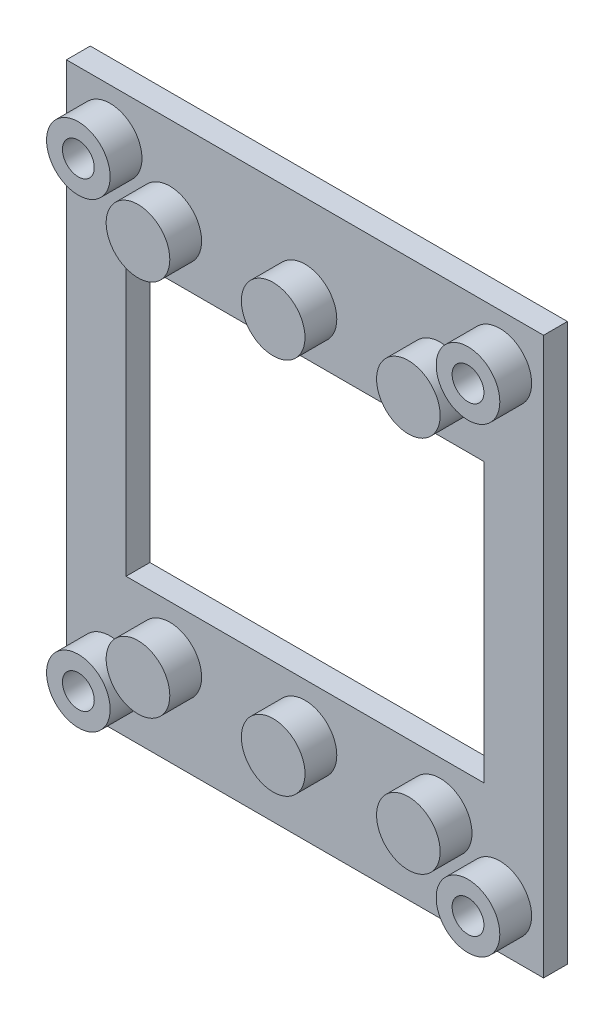
SolidWorks part; units mm, degrees
ref_plane "Plan de face" through (0, 0, 0) normal (0, 0, 1) x (1, 0, 0)
ref_plane "Plan de dessus" through (0, 0, 0) normal (0, 1, 0) x (1, 0, 0)
ref_plane "Plan de droite" through (0, 0, 0) normal (1, 0, 0) x (0, 0, -1)
sketch "Esquisse1" plane through (0, 0, 0) normal (0, 0, 1) x (1, 0, 0)
  line L1 (-30, 35) -> (30, 35)
  line L2 (-30, 35) -> (-30, -35)
  line L3 (-30, -35) -> (30, -35)
  line L4 (30, 35) -> (30, -35)
  line L5 (-30, 35) -> (30, -35) construction
  line L6 (-30, -35) -> (30, 35) construction
  point P0 (0, 0)
  dimension "D1" = 70
  dimension "D2" = 60
base flange "Tôle de base pliée1" sketch "Esquisse1" thickness 3 reverse thickness direction no parameters "D1"=2
sketch "Esquisse6" plane through (0, 0, 0) normal (0, 0, 1) x (1, 0, 0)
  line L1 (-24.5, 29) -> (24.5, 29) construction
  line L2 (-24.5, 29) -> (-24.5, -29) construction
  line L3 (-24.5, -29) -> (24.5, -29) construction
  line L4 (24.5, 29) -> (24.5, -29) construction
  line L5 (-24.5, 29) -> (24.5, -29) construction
  line L6 (-24.5, -29) -> (24.5, 29) construction
  circle A4 centre (-24.5, 29) radius 2
  circle A5 centre (24.5, 29) radius 2
  circle A6 centre (24.5, -29) radius 2
  circle A7 centre (-24.5, -29) radius 2
  point P0 (0, 0)
  dimension "D1" = 4
  dimension "D2" = 49
  dimension "D3" = 58
  dimension "D4" = 2
  dimension "D5" = 2
extrude "Enlèv. mat.-Extru.1" cut sketch "Esquisse6" against normal up to next normal cut yes
sketch "Esquisse7" plane through (0, 0, 0) normal (0, 0, 1) x (1, 0, 0)
  line L0 (0, 23.75) -> (0, -23.75) construction
  circle A0 centre (-17, -23.75) radius 2
  circle A1 centre (0, -23.75) radius 2
  circle A2 centre (17, -23.75) radius 2
  circle A3 centre (0, 23.75) radius 2
  circle A4 centre (17, 23.75) radius 2
  circle A5 centre (-17, 23.75) radius 2
  circle A6 centre (24.5, 29) radius 2 construction
  circle A7 centre (24.5, 29) radius 2 construction
  point P2 (0, 0)
  dimension "D1" = 4
  dimension "D4" = 34
  dimension "D5" = 47.5
  dimension "D2" = 3
  dimension "D3" = 2
extrude "Enlèv. mat.-Extru.2" cut sketch "Esquisse7" against normal up to next normal cut yes
sketch "Esquisse9" plane through (0, 0, 0) normal (0, 0, 1) x (1, 0, 0)
  circle A0 centre (-24.5, 29) radius 4
  circle A1 centre (24.5, 29) radius 4
  circle A2 centre (24.5, -29) radius 4
  circle A3 centre (-24.5, -29) radius 4
  circle A4 centre (-24.5, -29) radius 2 construction
  circle A5 centre (24.5, -29) radius 2 construction
  circle A6 centre (24.5, 29) radius 2 construction
  circle A7 centre (-24.5, 29) radius 2 construction
  circle A8 centre (-24.5, -29) radius 2
  circle A9 centre (24.5, -29) radius 2
  circle A10 centre (24.5, 29) radius 2
  circle A11 centre (-24.5, 29) radius 2
  dimension "D1" = 8
  dimension "D2" = 8
  dimension "D3" = 8
  dimension "D4" = 8
extrude "Boss.-Extru.1" add sketch "Esquisse9" along normal blind 4
sketch "Esquisse10" plane through (0, 0, 0) normal (0, 0, 1) x (1, 0, 0)
  line L1 (-22.5, 17.5) -> (22.5, 17.5)
  line L2 (-22.5, 17.5) -> (-22.5, -17.5)
  line L3 (-22.5, -17.5) -> (22.5, -17.5)
  line L4 (22.5, 17.5) -> (22.5, -17.5)
  line L5 (-22.5, 17.5) -> (22.5, -17.5) construction
  line L6 (-22.5, -17.5) -> (22.5, 17.5) construction
  point P0 (0, 0)
  dimension "D1" = 35
  dimension "D2" = 45
extrude "Enlèv. mat.-Extru.3" cut sketch "Esquisse10" against normal up to next normal cut yes
sketch "Esquisse11" plane through (0, 0, -3) normal (0, 0, -1) x (-1, 0, 0)
  circle A0 centre (-24.5, -29) radius 2 construction
  circle A1 centre (24.5, -29) radius 2 construction
  circle A2 centre (24.5, 29) radius 2 construction
  circle A3 centre (-24.5, 29) radius 2 construction
  circle A4 centre (-24.5, -29) radius 2
  circle A5 centre (24.5, -29) radius 2
  circle A6 centre (24.5, 29) radius 2
  circle A7 centre (-24.5, 29) radius 2
extrude "Boss.-Extru.2" add sketch "Esquisse11" against normal blind 1
sketch "Esquisse12" plane through (0, 0, 0) normal (0, 0, 1) x (1, 0, 0)
  circle A0 centre (-17, -23.75) radius 2 construction
  circle A1 centre (0, -23.75) radius 2 construction
  circle A2 centre (17, -23.75) radius 2 construction
  circle A3 centre (17, 23.75) radius 2 construction
  circle A4 centre (0, 23.75) radius 2 construction
  circle A5 centre (-17, 23.75) radius 2 construction
  circle A6 centre (-17, -23.75) radius 2
  circle A7 centre (0, -23.75) radius 2
  circle A8 centre (17, -23.75) radius 2
  circle A9 centre (17, 23.75) radius 2
  circle A10 centre (0, 23.75) radius 2
  circle A11 centre (-17, 23.75) radius 2
  circle A12 centre (-17, 23.75) radius 4
  circle A13 centre (0, 23.75) radius 4
  circle A14 centre (17, 23.75) radius 4
  circle A15 centre (17, -23.75) radius 4
  circle A16 centre (0, -23.75) radius 4
  circle A17 centre (-17, -23.75) radius 4
  dimension "D1" = 8
  dimension "D2" = 8
  dimension "D3" = 8
  dimension "D4" = 8
  dimension "D5" = 8
  dimension "D6" = 8
extrude "Boss.-Extru.3" add sketch "Esquisse12" along normal blind 3
sketch "Esquisse13" plane through (0, 0, 3) normal (0, 0, 1) x (1, 0, 0)
  circle A0 centre (-17, -23.75) radius 4 construction
  circle A1 centre (0, -23.75) radius 4 construction
  circle A2 centre (17, -23.75) radius 4 construction
  circle A3 centre (17, 23.75) radius 4 construction
  circle A4 centre (0, 23.75) radius 4 construction
  circle A5 centre (-17, 23.75) radius 4 construction
  circle A6 centre (-17, -23.75) radius 4
  circle A7 centre (0, -23.75) radius 4
  circle A8 centre (17, -23.75) radius 4
  circle A9 centre (17, 23.75) radius 4
  circle A10 centre (0, 23.75) radius 4
  circle A11 centre (-17, 23.75) radius 4
extrude "Boss.-Extru.4" add sketch "Esquisse13" along normal blind 1
sketch "Lignes de pliage1" [suppressed] plane through (0, 0, 0) normal (0, 1, 0) x (1, 0, 0)
sketch "Cube de visualisation1" [suppressed] plane through (0, 0, 0) normal (0, 1, 0) x (1, 0, 0)
sheet metal parameters "Tôlerie1" thickness 3 parameters "D1"=2
flat pattern "Etat déplié1" [suppressed]
sketch "Lignes de pliage2" plane through (0, 0, 0) normal (0, 1, 0) x (1, 0, 0)
sketch3d "Cube de visualisation2" [suppressed]
  line L0 (-35, -35, 0) -> (35, -35, 0) construction
  line L1 (-35, 35, 0) -> (35, 35, 0) construction
  line L2 (-35, -35, 0) -> (-35, 35, 0) construction
  line L3 (35, -35, 0) -> (35, 35, 0) construction
sheet metal parameters "Tôlerie2" thickness 3 parameters "D1"=2
flat pattern "Etat déplié1"
sketch "Lignes de pliage2" plane through (0, 0, 0) normal (0, 1, 0) x (1, 0, 0)
sketch3d "Cube de visualisation2" [suppressed]
  line L0 (-35, -35, 0) -> (35, -35, 0) construction
  line L1 (-35, 35, 0) -> (35, 35, 0) construction
  line L2 (-35, -35, 0) -> (-35, 35, 0) construction
  line L3 (35, -35, 0) -> (35, 35, 0) construction
sheet metal parameters "Tôlerie3" thickness 3 parameters "D1"=2
flat pattern "Etat déplié1"
sketch "Lignes de pliage2" plane through (0, 0, 0) normal (0, 1, 0) x (1, 0, 0)
sketch3d "Cube de visualisation2" [suppressed]
  line L0 (27.5, 32.5, 0) -> (27.5, -32.5, 0) construction
  line L1 (-27.5, 32.5, 0) -> (-27.5, -32.5, 0) construction
  line L2 (27.5, 32.5, 0) -> (-27.5, 32.5, 0) construction
  line L3 (27.5, -32.5, 0) -> (-27.5, -32.5, 0) construction
sheet metal parameters "Tôlerie4" thickness 3 parameters "D1"=2
flat pattern "Etat déplié1"
sketch "Lignes de pliage2" plane through (0, 0, 0) normal (0, 1, 0) x (1, 0, 0)
sketch3d "Cube de visualisation2" [suppressed]
  line L0 (30, 35, 0) -> (30, -35, 0) construction
  line L1 (-30, 35, 0) -> (-30, -35, 0) construction
  line L2 (30, 35, 0) -> (-30, 35, 0) construction
  line L3 (30, -35, 0) -> (-30, -35, 0) construction
sheet metal parameters "Tôlerie5" thickness 3 parameters "D1"=2
flat pattern "Etat déplié1"
sketch "Lignes de pliage2" plane through (0, 0, 0) normal (0, 1, 0) x (1, 0, 0)
sketch3d "Cube de visualisation2" [suppressed]
  line L0 (30, 35, 0) -> (30, -35, 0) construction
  line L1 (-30, 35, 0) -> (-30, -35, 0) construction
  line L2 (30, 35, 0) -> (-30, 35, 0) construction
  line L3 (30, -35, 0) -> (-30, -35, 0) construction
sheet metal parameters "Tôlerie6" thickness 3 parameters "D1"=2
flat pattern "Etat déplié1"
sketch "Lignes de pliage2" plane through (0, 0, 0) normal (0, 1, 0) x (1, 0, 0)
sketch3d "Cube de visualisation2" [suppressed]
  line L0 (30, 35, 0) -> (30, -35, 0) construction
  line L1 (-30, 35, 0) -> (-30, -35, 0) construction
  line L2 (30, 35, 0) -> (-30, 35, 0) construction
  line L3 (30, -35, 0) -> (-30, -35, 0) construction
sheet metal parameters "Tôlerie7" thickness 3 parameters "D1"=2
flat pattern "Etat déplié1"
sketch "Lignes de pliage2" plane through (0, 0, 0) normal (0, 1, 0) x (1, 0, 0)
sketch3d "Cube de visualisation2" [suppressed]
  line L0 (30, 35, 0) -> (30, -35, 0) construction
  line L1 (-30, 35, 0) -> (-30, -35, 0) construction
  line L2 (30, 35, 0) -> (-30, 35, 0) construction
  line L3 (30, -35, 0) -> (-30, -35, 0) construction
sheet metal parameters "Tôlerie8" thickness 3 parameters "D1"=2
flat pattern "Etat déplié1"
sketch "Lignes de pliage2" plane through (0, 0, 0) normal (0, 1, 0) x (1, 0, 0)
sketch3d "Cube de visualisation2" [suppressed]
  line L0 (30, 35, 0) -> (30, -35, 0) construction
  line L1 (-30, 35, 0) -> (-30, -35, 0) construction
  line L2 (30, 35, 0) -> (-30, 35, 0) construction
  line L3 (30, -35, 0) -> (-30, -35, 0) construction
equation "\"D2@Esquisse9\"=\"D1@Esquisse9\""
equation "\"D3@Esquisse9\"=\"D1@Esquisse9\""
equation "\"D4@Esquisse9\"=\"D1@Esquisse9\""
equation "\"D2@Esquisse12\"=\"D1@Esquisse12\""
equation "\"D3@Esquisse12\"=\"D1@Esquisse12\""
equation "\"D4@Esquisse12\"=\"D3@Esquisse12\""
equation "\"D5@Esquisse12\"=\"D2@Esquisse12\""
equation "\"D6@Esquisse12\"=\"D1@Esquisse12\""
